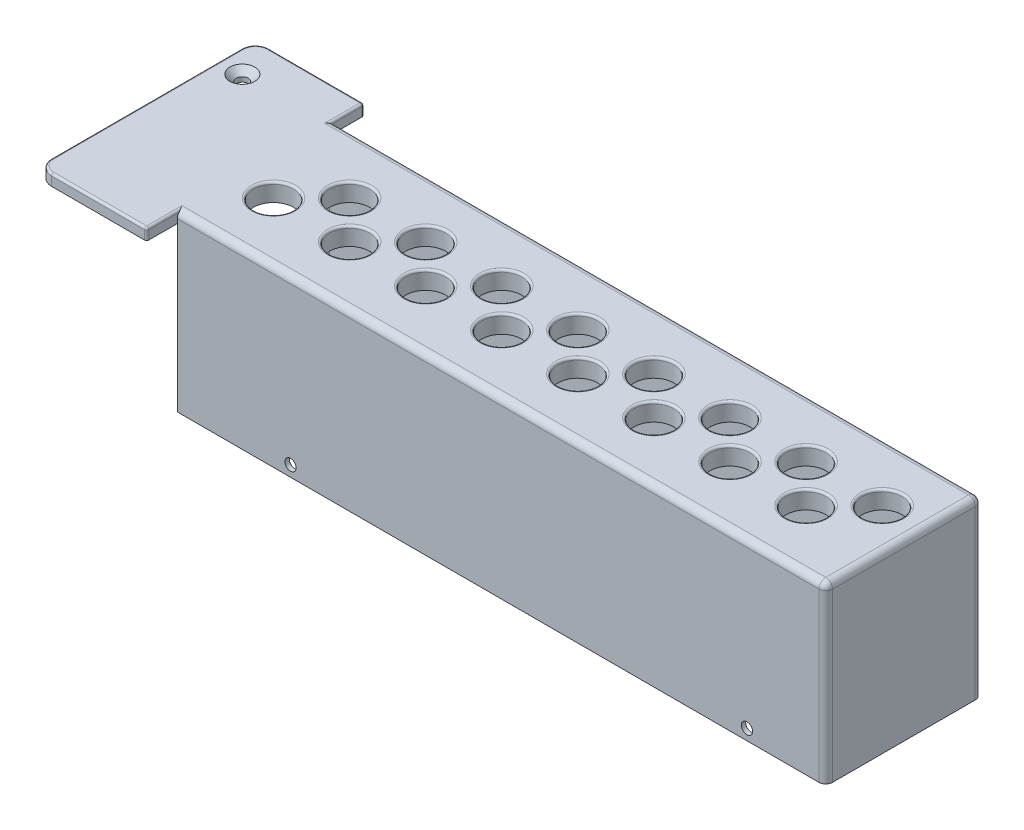
SolidWorks part; units mm, degrees
material "PBT General Purpose"
ref_plane "Front Plane" through (0, 0, 0) normal (0, 0, 1) x (1, 0, 0)
ref_plane "Top Plane" through (0, 0, 0) normal (0, 1, 0) x (1, 0, 0)
ref_plane "Right Plane" through (0, 0, 0) normal (1, 0, 0) x (0, 0, -1)
sketch "Sketch1" plane through (0, 0, 0) normal (0, 1, 0) x (1, 0, 0)
  line L1 (0, 0) -> (307.975, 0)
  line L2 (0, 0) -> (0, -73.025)
  line L3 (0, -73.025) -> (307.975, -73.025)
  line L4 (307.975, 0) -> (307.975, -73.025)
  line L7 (0, -36.5125) -> (25.4, -36.5125) construction
  line L45 (271.145, -36.5125) -> (271.145, -27.6225) construction
  line L46 (288.925, -27.6225) -> (271.145, -27.6225) construction
  line L47 (271.145, -36.5125) -> (280.035, -36.5125) construction
  line L48 (271.145, -45.4025) -> (271.145, -36.5125) construction
  line L49 (271.145, -45.4025) -> (288.925, -27.6225) construction
  line L50 (235.585, -36.5125) -> (235.585, -27.6225) construction
  line L51 (253.365, -27.6225) -> (235.585, -27.6225) construction
  line L52 (235.585, -36.5125) -> (244.475, -36.5125) construction
  line L53 (235.585, -45.4025) -> (235.585, -36.5125) construction
  line L54 (235.585, -45.4025) -> (253.365, -27.6225) construction
  line L55 (200.025, -36.5125) -> (200.025, -27.6225) construction
  line L56 (217.805, -27.6225) -> (200.025, -27.6225) construction
  line L57 (200.025, -36.5125) -> (208.915, -36.5125) construction
  line L58 (200.025, -45.4025) -> (200.025, -36.5125) construction
  line L59 (200.025, -45.4025) -> (217.805, -27.6225) construction
  line L60 (164.465, -36.5125) -> (164.465, -27.6225) construction
  line L61 (182.245, -27.6225) -> (164.465, -27.6225) construction
  line L62 (164.465, -36.5125) -> (173.355, -36.5125) construction
  line L63 (164.465, -45.4025) -> (164.465, -36.5125) construction
  line L64 (164.465, -45.4025) -> (182.245, -27.6225) construction
  line L65 (128.905, -36.5125) -> (128.905, -27.6225) construction
  line L66 (146.685, -27.6225) -> (128.905, -27.6225) construction
  line L67 (128.905, -36.5125) -> (137.795, -36.5125) construction
  line L68 (128.905, -45.4025) -> (128.905, -36.5125) construction
  line L69 (128.905, -45.4025) -> (146.685, -27.6225) construction
  line L70 (93.345, -36.5125) -> (93.345, -27.6225) construction
  line L71 (111.125, -27.6225) -> (93.345, -27.6225) construction
  line L72 (93.345, -36.5125) -> (102.235, -36.5125) construction
  line L73 (93.345, -45.4025) -> (93.345, -36.5125) construction
  line L74 (93.345, -45.4025) -> (111.125, -27.6225) construction
  line L75 (57.785, -36.5125) -> (57.785, -27.6225) construction
  line L76 (75.565, -27.6225) -> (57.785, -27.6225) construction
  line L77 (57.785, -36.5125) -> (66.675, -36.5125) construction
  line L78 (57.785, -45.4025) -> (57.785, -36.5125) construction
  line L79 (57.785, -45.4025) -> (75.565, -27.6225) construction
  line L80 (22.225, -36.5125) -> (22.225, -27.6225) construction
  line L81 (40.005, -27.6225) -> (22.225, -27.6225) construction
  line L82 (22.225, -36.5125) -> (31.115, -36.5125) construction
  line L83 (22.225, -45.4025) -> (22.225, -36.5125) construction
  line L84 (22.225, -45.4025) -> (40.005, -27.6225) construction
  circle A16 centre (288.925, -27.6225) radius 9.3345
  circle A17 centre (271.145, -45.4025) radius 9.3345
  circle A18 centre (253.365, -27.6225) radius 9.3345
  circle A19 centre (235.585, -45.4025) radius 9.3345
  circle A20 centre (217.805, -27.6225) radius 9.3345
  circle A21 centre (200.025, -45.4025) radius 9.3345
  circle A22 centre (182.245, -27.6225) radius 9.3345
  circle A23 centre (164.465, -45.4025) radius 9.3345
  circle A24 centre (146.685, -27.6225) radius 9.3345
  circle A25 centre (128.905, -45.4025) radius 9.3345
  circle A26 centre (111.125, -27.6225) radius 9.3345
  circle A27 centre (93.345, -45.4025) radius 9.3345
  circle A28 centre (75.565, -27.6225) radius 9.3345
  circle A29 centre (57.785, -45.4025) radius 9.3345
  circle A30 centre (40.005, -27.6225) radius 9.3345
  circle A31 centre (22.225, -45.4025) radius 9.3345
  dimension "D3" = 17.78
  dimension "D1" = 307.975
  dimension "D2" = 73.025
  dimension "D4" = 45
  dimension "D5" = 8.89
  dimension "D7" = 18.669
extrude "Boss-Extrude1" add sketch "Sketch1" against normal blind 2.032
sketch "Sketch2" plane through (0, -2.032, 0) normal (0, -1, 0) x (1, 0, 0)
  line L0 (305.943, 70.993) -> (2.032, 70.993)
  line L1 (2.032, 70.993) -> (2.032, 2.032)
  line L2 (2.032, 2.032) -> (305.943, 2.032)
  line L3 (305.943, 2.032) -> (305.943, 70.993)
  line L4 (0, 73.025) -> (0, 0)
  line L5 (0, 0) -> (307.975, 0)
  line L6 (307.975, 0) -> (307.975, 73.025)
  line L7 (307.975, 73.025) -> (0, 73.025)
  line L8 (0, 73.025) -> (0, 0)
  line L9 (0, 0) -> (307.975, 0)
  line L10 (307.975, 0) -> (307.975, 73.025)
  line L11 (307.975, 73.025) -> (0, 73.025)
  dimension "D2" = 2.032
  dimension "D1" = 0
extrude "Boss-Extrude2" add sketch "Sketch2" along normal blind 79.375
fillet "Fillet1" radius 3.175 8 edges at (307.975, 0, 36.5125) (153.9875, 0, 73.025) (153.9875, 0, 0) (0, 0, 36.5125) (0, -40.7035, 0) (0, -40.7035, 73.025) (307.975, -40.7035, 0) (307.975, -40.7035, 73.025)
sketch "Sketch3" plane through (0, -2.032, 0) normal (0, -1, 0) x (1, 0, 0)
  line L0 (0, 36.5125) -> (307.975, 36.5125) construction
  line L1 (0, 69.85) -> (0, 3.175) construction
  line L2 (307.975, 3.175) -> (307.975, 69.85) construction
  circle A0 centre (22.225, 45.4025) radius 9.8425
  circle A1 centre (40.005, 27.6225) radius 9.8425
  circle A54 centre (57.785, 45.4025) radius 9.8425
  circle A55 centre (75.565, 27.6225) radius 9.8425
  circle A56 centre (93.345, 45.4025) radius 9.8425
  circle A57 centre (111.125, 27.6225) radius 9.8425
  circle A58 centre (128.905, 45.4025) radius 9.8425
  circle A59 centre (146.685, 27.6225) radius 9.8425
  circle A60 centre (164.465, 45.4025) radius 9.8425
  circle A61 centre (182.245, 27.6225) radius 9.8425
  circle A62 centre (200.025, 45.4025) radius 9.8425
  circle A63 centre (217.805, 27.6225) radius 9.8425
  circle A64 centre (235.585, 45.4025) radius 9.8425
  circle A65 centre (253.365, 27.6225) radius 9.8425
  circle A66 centre (271.145, 45.4025) radius 9.8425
  circle A67 centre (288.925, 27.6225) radius 9.8425
  circle A68 centre (22.225, 45.4025) radius 9.3345
  circle A69 centre (40.005, 27.6225) radius 9.3345
  circle A70 centre (57.785, 45.4025) radius 9.3345
  circle A71 centre (75.565, 27.6225) radius 9.3345
  circle A72 centre (93.345, 45.4025) radius 9.3345
  circle A73 centre (111.125, 27.6225) radius 9.3345
  circle A74 centre (128.905, 45.4025) radius 9.3345
  circle A75 centre (146.685, 27.6225) radius 9.3345
  circle A76 centre (164.465, 45.4025) radius 9.3345
  circle A77 centre (182.245, 27.6225) radius 9.3345
  circle A78 centre (200.025, 45.4025) radius 9.3345
  circle A79 centre (217.805, 27.6225) radius 9.3345
  circle A80 centre (235.585, 45.4025) radius 9.3345
  circle A81 centre (253.365, 27.6225) radius 9.3345
  circle A82 centre (271.145, 45.4025) radius 9.3345
  circle A83 centre (288.925, 27.6225) radius 9.3345
extrude "Boss-Extrude3" add sketch "Sketch3" along normal blind 6.35
sketch "Sketch4" plane through (0, 0, 73.025) normal (0, 0, 1) x (1, 0, 0)
  line L5 (3.8329, -81.407) -> (303.2125, -81.407) construction
  line L6 (4.8489, -81.407) -> (-26.5031, -81.407)
  line L7 (4.8489, -81.407) -> (4.8489, 6.2068)
  line L8 (4.8489, 6.2068) -> (-26.5031, 6.2068)
  line L9 (-26.5031, -81.407) -> (-26.5031, 6.2068)
  line L10 (4.8489, -5.207) -> (4.8489, -81.407) construction
extrude "Cut-Extrude1" cut sketch "Sketch4" against normal through all
sketch "Sketch5" plane through (0, 0, 0) normal (0, 1, 0) x (1, 0, 0)
  line L0 (4.8489, 0) -> (304.8, 0) construction
  line L5 (4.8489, -86.2965) -> (4.8489, 13.2715)
  line L6 (3.8329, 14.2875) -> (-39.6011, 14.2875)
  line L7 (-45.9511, 7.9375) -> (-45.9511, -80.9625)
  line L8 (-39.6011, -87.3125) -> (3.8329, -87.3125)
  arc A4 (4.8489, 13.2715) -> (3.8329, 14.2875) centre (3.8329, 13.2715) ccw
  arc A5 (-39.6011, 14.2875) -> (-45.9511, 7.9375) centre (-39.6011, 7.9375) ccw
  arc A6 (-45.9511, -80.9625) -> (-39.6011, -87.3125) centre (-39.6011, -80.9625) ccw
  arc A7 (3.8329, -87.3125) -> (4.8489, -86.2965) centre (3.8329, -86.2965) ccw
  dimension "D5" = 6.35
  dimension "D6" = 6.35
  dimension "D7" = 1.016
  dimension "D8" = 1.016
  dimension "D1" = 50.8
  dimension "D2" = 14.2875
  dimension "D3" = 101.6
  dimension "D4" = 4.8489
  dimension "D9" = 14.2875
extrude "Boss-Extrude4" add sketch "Sketch5" against normal blind 5.207
sketch "Sketch6" plane through (0, 0, 0) normal (0, 1, 0) x (1, 0, 0)
  line L0 (-45.9511, 7.9375) -> (-45.9511, -80.9625) construction
  line L1 (3.8329, 14.2875) -> (-39.6011, 14.2875) construction
  circle A0 centre (-35.2323, -2.5304) radius 2.794
  dimension "D1" = 10.7188
  dimension "D3" = 5.588
  dimension "D2" = 16.8179
extrude "Cut-Extrude2" cut sketch "Sketch6" against normal through all
chamfer "Chamfer1" distance 3.0162 angle 45 1 edges at (-35.2323, 0, 5.3244)
fillet "Fillet2" radius 1.016 25 edges at (4.8489, 0, 78.0733) (4.8489, 0, -5.0482) (4.5513, 0, -13.9899) (-17.8841, 0, -14.2875) (-44.0912, 0, -12.4276) (-44.0912, 0, 85.4526) (-45.9511, 0, 36.5125) (-17.8841, 0, 87.3125) (4.5513, 0, 87.0149) (288.925, 0, 18.288) (271.145, 0, 36.068) (253.365, 0, 18.288) (235.585, 0, 36.068) (200.025, 0, 36.068) (217.805, 0, 18.288) (182.245, 0, 18.288) (164.465, 0, 36.068) (146.685, 0, 18.288) (128.905, 0, 36.068) (111.125, 0, 18.288) (93.345, 0, 36.068) (75.565, 0, 18.288) (57.785, 0, 36.068) (22.225, 0, 36.068) (40.005, 0, 18.288)
sketch "Sketch7" plane through (0, -5.207, 0) normal (0, -1, 0) x (1, 0, 0)
  line L8 (4.8489, 2.032) -> (2.8169, 2.032)
  line L9 (4.8489, 70.993) -> (2.8169, 70.993)
  line L10 (4.8489, 70.993) -> (4.8489, 2.032)
  line L16 (2.8169, -12.2555) -> (2.8169, 0)
  line L17 (2.8169, 0) -> (2.8169, 2.032)
  line L18 (2.8169, 2.032) -> (2.8169, 70.993)
  line L19 (2.8169, 70.993) -> (2.8169, 73.025)
  line L20 (2.8169, 73.025) -> (2.8169, 85.2805)
  line L21 (2.8169, 85.2805) -> (-39.6011, 85.2805)
  line L22 (-43.9191, 80.9625) -> (-43.9191, -7.9375)
  line L23 (-39.6011, -12.2555) -> (2.8169, -12.2555)
  line L24 (2.8169, -12.2555) -> (2.8169, 0)
  line L25 (2.8169, 0) -> (2.8169, 2.032)
  line L27 (2.8169, 70.993) -> (2.8169, 73.025)
  line L28 (2.8169, 73.025) -> (2.8169, 85.2805)
  line L29 (2.8169, 85.2805) -> (-39.6011, 85.2805)
  line L30 (-43.9191, 80.9625) -> (-43.9191, -7.9375)
  line L31 (-39.6011, -12.2555) -> (2.8169, -12.2555)
  circle A6 centre (-35.2323, 2.5304) radius 5.08
  arc A10 (-39.6011, 85.2805) -> (-43.9191, 80.9625) centre (-39.6011, 80.9625) ccw
  arc A11 (-43.9191, -7.9375) -> (-39.6011, -12.2555) centre (-39.6011, -7.9375) ccw
  arc A14 (-39.6011, 85.2805) -> (-43.9191, 80.9625) centre (-39.6011, 80.9625) ccw
  arc A15 (-43.9191, -7.9375) -> (-39.6011, -12.2555) centre (-39.6011, -7.9375) ccw
  dimension "D2" = 10.16
  dimension "D1" = 2.032
extrude "Cut-Extrude3" cut sketch "Sketch7" against normal up to surface (3.175 mm away) up to face at (271.145, -2.032, 55.245)
sketch "Sketch8" plane through (0, 0, 73.025) normal (0, 0, 1) x (1, 0, 0)
  line L0 (57.785, -76.327) -> (271.145, -76.327) construction
  line L2 (304.8, -81.407) -> (4.8489, -81.407) construction
  line L3 (57.785, -65.3034) -> (57.785, -83.7882) construction
  line L5 (271.145, -65.3034) -> (271.145, -83.7882) construction
  circle A0 centre (57.785, -76.327) radius 2.6162
  circle A1 centre (271.145, -76.327) radius 2.6162
  dimension "D1" = 5.2324
  dimension "D2" = 5.2324
  dimension "D3" = 213.36
  dimension "D5" = 5.08
extrude "Cut-Extrude4" cut sketch "Sketch8" against normal blind 12.7
sketch "Sketch9" plane through (0, 0, 0) normal (0, 0, -1) x (-1, 0, 0)
  circle A0 centre (-253.365, -76.327) radius 2.5781
  circle A1 centre (-40.005, -76.327) radius 2.5781
extrude "Cut-Extrude5" cut sketch "Sketch9" against normal blind 12.7
sketch "Sketch11" plane through (0, 0, -14.2875) normal (0, 0, -1) x (-1, 0, 0)
  line L0 (-3.8329, -5.207) -> (39.6011, -5.207) construction
  line L1 (25.7327, -5.207) -> (38.2295, -5.207)
  line L2 (25.7327, -5.207) -> (25.7327, -16.891)
  line L3 (25.7327, -16.891) -> (38.2295, -16.891)
  line L4 (38.2295, -5.207) -> (38.2295, -16.891)
  line L5 (45.9511, -5.207) -> (45.9511, -1.016) construction
  dimension "D1" = 7.7216
  dimension "D2" = 12.4968
  dimension "D3" = 11.684
extrude "Boss-Extrude5" add sketch "Sketch11" against normal blind 2.032
